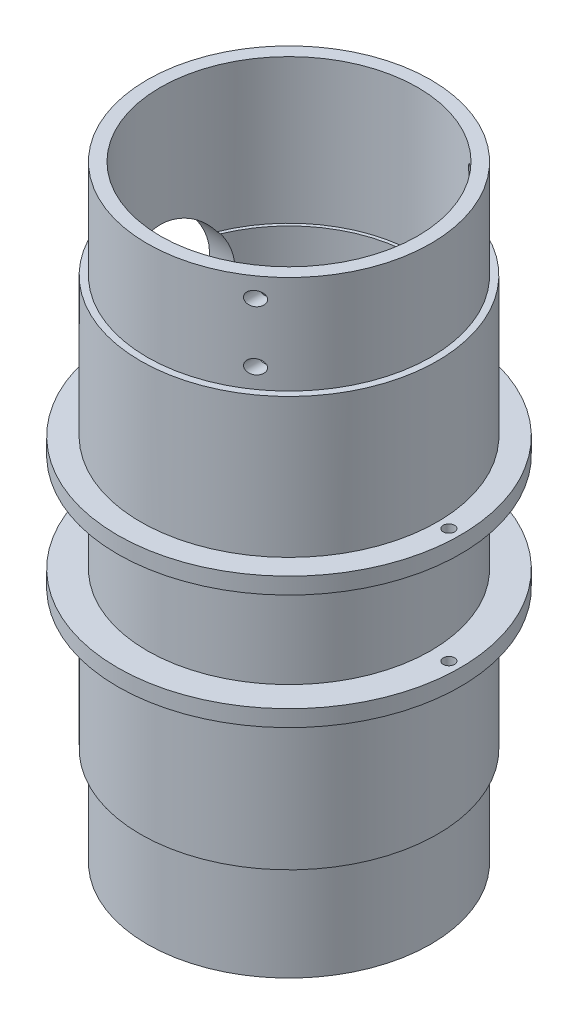
SolidWorks part; units mm, degrees
ref_plane "Front Plane" through (0, 0, 0) normal (0, 0, 1) x (1, 0, 0)
ref_plane "Top Plane" through (0, 0, 0) normal (0, 1, 0) x (1, 0, 0)
ref_plane "Right Plane" through (0, 0, 0) normal (1, 0, 0) x (0, 0, -1)
sketch "Sketch1" plane through (0, 0, 0) normal (0, 1, 0) x (1, 0, 0)
  line L0 (0, 38.25) -> (0, 45.25) construction
  circle A0 centre (0, 0) radius 38.25
  circle A1 centre (0, 0) radius 45.25
  dimension "D1" = 76.5
  dimension "D2" = 7
extrude "Boss-Extrude1" add sketch "Sketch1" along normal mid plane 185
sketch "Sketch2" plane through (0, -92.5, 0) normal (0, -1, 0) x (1, 0, 0)
  line L0 (0, 36.25) -> (0, 38.25) construction
  circle A0 centre (0, 0) radius 36.25
  circle A1 centre (0, 0) radius 38.25 construction
  circle A2 centre (0, 0) radius 38.25
  dimension "D1" = 2
extrude "Boss-Extrude2" add sketch "Sketch2" against normal blind 100 from offset 6.35 offset against normal yes
sketch "Sketch6" plane through (0, 92.5, 0) normal (0, 1, 0) x (1, 0, 0)
  line L0 (0, 38.25) -> (0, 39.25) construction
  circle A0 centre (0, 0) radius 39.25
  circle A1 centre (0, 0) radius 38.25 construction
  circle A2 centre (0, 0) radius 38.25
  dimension "D1" = 1
extrude "Cut-Extrude3" cut sketch "Sketch6" against normal blind 44
sketch "Sketch7" plane through (0, 0, 0) normal (1, 0, 0) x (0, 0, -1)
  line L0 (45.25, 92.5) -> (-45.25, 92.5) construction
  circle A0 centre (0, 38.75) radius 17.5
  dimension "D2" = 35
  dimension "D1" = 53.75
extrude "Cut-Extrude4" cut sketch "Sketch7" against normal through all
sketch "Sketch8" plane through (0, 92.5, 0) normal (0, 1, 0) x (1, 0, 0)
  line L0 (0, 43.25) -> (0, 45.25) construction
  circle A0 centre (0, 0) radius 45.25 construction
  circle A1 centre (0, 0) radius 45.25
  circle A2 centre (0, 0) radius 43.25
  dimension "D1" = 2
extrude "Cut-Extrude5" cut sketch "Sketch8" against normal blind 30
mirror "Mirror1" about plane through (0, 0, 0) normal (0, 1, 0) of "Cut-Extrude5"
sketch "Sketch9" plane through (0, 0, 0) normal (0, 1, 0) x (1, 0, 0)
  circle A1 centre (0, 0) radius 43.25
  circle A2 centre (0, 0) radius 43.25
  circle A3 centre (0, 0) radius 45.25
  circle A4 centre (0, 0) radius 45.25
  dimension "D1" = 0
  dimension "D2" = 0
extrude "Cut-Extrude6" cut sketch "Sketch9" against normal mid plane 30
ref_plane "Plane1" through (0, 15, 0) normal (0, -1, 0) x (-1, 0, 0)
sketch "Sketch10" plane through (0, 15, 0) normal (0, -1, 0) x (-1, 0, 0)
  circle A0 centre (0, 0) radius 52.25
  circle A1 centre (0, 0) radius 43.25
  circle A2 centre (-48.75, 0) radius 1.75
  point P6 (-48.25, 0)
  dimension "D1" = 48.75
  dimension "D2" = 3.5
extrude "Boss-Extrude3" add sketch "Sketch10" against normal blind 5
ref_plane "Plane2" through (0, 0, 0) normal (0, 1, 0) x (1, 0, 0)
mirror "Mirror2" about plane through (0, 0, 0) normal (0, 1, 0) of "Boss-Extrude3"
hole_wizard "CBORE for M4 SHCS1" positions "Sketch15" profile "Sketch16" counterbore size "M4" standard "ANSI Metric"
sketch "Sketch15" plane through (632.5589, 23.278, 50.0506) normal (0, 0, 1) x (-0.3467, 0.938, 0)
  line L0 (253.0708, 554.1913) -> (269.9543, 547.9503) construction
  line L2 (261.5125, 551.0708) -> (258.0453, 541.6911) construction
  circle A0 centre (253.0708, 554.1913) radius 2.25
  circle A1 centre (269.9543, 547.9503) radius 2.25
  point P0 (253.0708, 554.1913)
  point P2 (269.9543, 547.9503)
sketch "Sketch16" plane through (25, 68.5, 50.0506) normal (1, 0, 0) x (0, -1, 0)
  line L0 (0, 0) -> (0, 101.393)
  line L1 (0, 101.393) -> (2.15, 100.1012)
  line L2 (2.15, 100.1012) -> (2.15, 4)
  line L3 (2.15, 4) -> (4, 4)
  line L4 (4, 4) -> (4, 0)
  line L5 (4, 0) -> (0, 0)
  line L6 (0, 101.393) -> (-2.15, 100.1012) construction
  line L7 (0, -6.35) -> (0, 107.95) construction
  dimension "Hole Dia." = 4.3
  dimension "Hole Depth" = 100.1012
  dimension "C'Bore Dia." = 8
  dimension "C'Bore Depth" = 4
  dimension "Drill Angle" = 118
